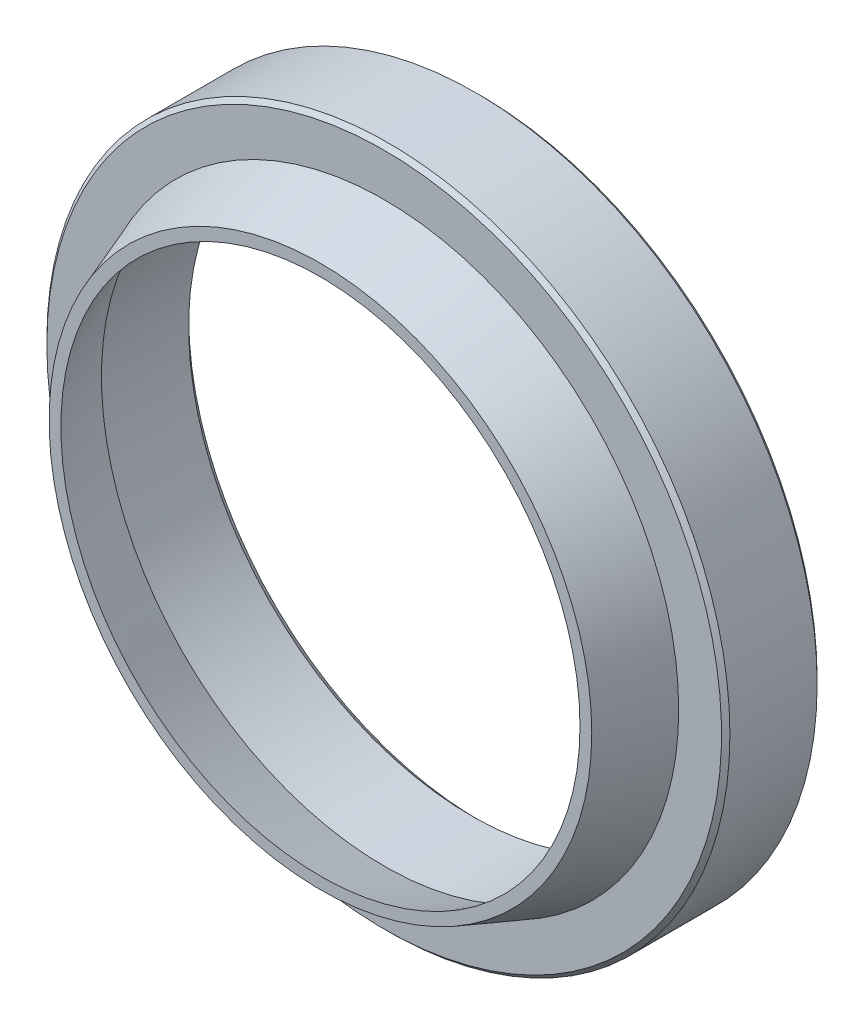
SolidWorks part; units mm, degrees
ref_plane "Front" through (0, 0, 0) normal (0, 0, 1) x (1, 0, 0)
ref_plane "Top" through (0, 0, 0) normal (0, 1, 0) x (1, 0, 0)
ref_plane "Right" through (0, 0, 0) normal (1, 0, 0) x (0, 0, -1)
sketch "Sketch1" plane through (25, 0, -4.5162) normal (0, 1, 0) x (-1, 0, 0)
  line L0 (25, 9.1959) -> (25, -4.6797) construction
  line L1 (45.7, -7.1505) -> (45.7, -0.1545)
  line L2 (45.7, -7.1505) -> (50, -7.1505)
  line L3 (45.7, -0.1545) -> (44, 4.5162)
  line L4 (46.56, -0.1505) -> (50, -0.1505)
  line L5 (50, -7.1505) -> (50, -0.1505)
  line L6 (44, 4.5162) -> (44.8615, 4.5162)
  line L7 (44.8615, 4.5162) -> (46.56, -0.1505)
  dimension "D1" = 38
  dimension "D5" = 160
  dimension "D6" = 0.86
  dimension "D7" = 4.6667
revolve "Body" add sketch "Sketch1" angle 360 about L0
chamfer "EndChamfer" distance 0.6143 angle 45 1 edges at (20.7, 0, -11.6667)
chamfer "BodyChamfer" distance 0.3071 angle 45 2 edges at (25, 0, -4.6667) (25, 0, -11.6667)
equation "\"D7@Sketch1\" = 2*\"h@Sketch1\" / 3"
equation "\"D6@Sketch1\" = \"S@Sketch1\" / 5"
equation "\"D1@EndChamfer\" = \"S@Sketch1\" / 7"
equation "\"D1@BodyChamfer\" = \"S@Sketch1\" / 14"
